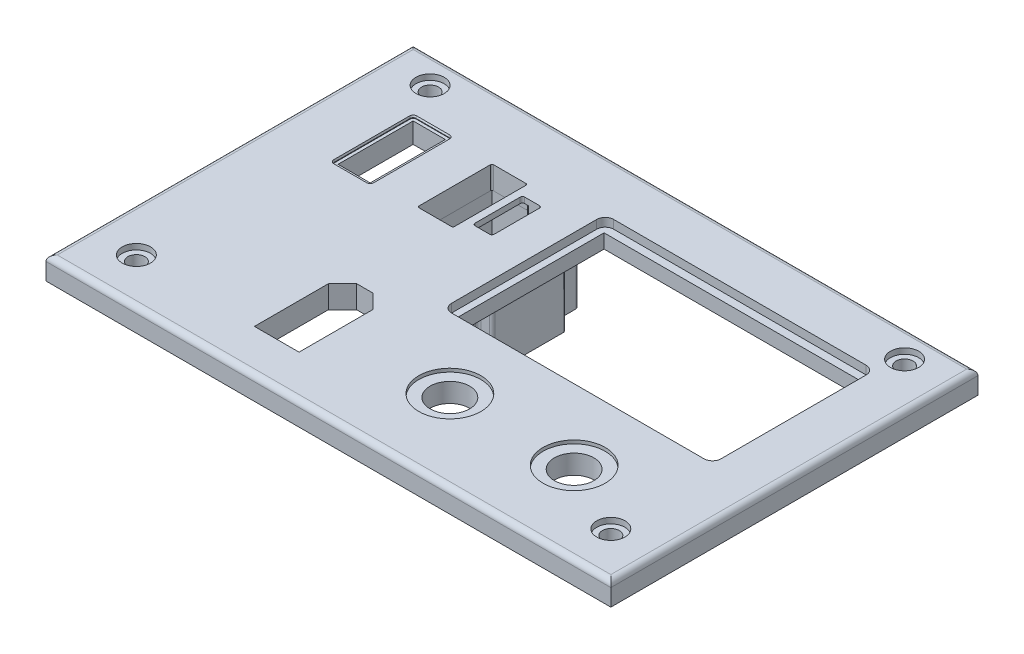
SolidWorks part; units mm, degrees
ref_plane "Спереди" through (0, 0, 0) normal (0, 0, 1) x (1, 0, 0)
ref_plane "Сверху" through (0, 0, 0) normal (0, 1, 0) x (1, 0, 0)
ref_plane "Справа" through (0, 0, 0) normal (1, 0, 0) x (0, 0, -1)
sketch "Эскиз1" plane through (0, 0, 0) normal (0, 1, 0) x (1, 0, 0)
  line L1 (-60, 30) -> (40, 30)
  line L2 (-60, 30) -> (-60, -35)
  line L3 (-60, -35) -> (40, -35)
  line L4 (40, 30) -> (40, -35)
  line L5 (-60, 30) -> (40, -35) construction
  line L6 (-60, -35) -> (40, 30) construction
  point P0 (0, 0)
  dimension "D1" = 65
  dimension "D2" = 100
extrude "Передняя панель основа" add sketch "Эскиз1" along normal blind 4
sketch "Эскиз2" plane through (0, 4, 0) normal (0, 1, 0) x (1, 0, 0)
  line L1 (31, 20.7) -> (-16.7, 20.7)
  line L2 (31, 20.7) -> (31, -8)
  line L3 (31, -8) -> (-16.7, -8)
  line L4 (-16.7, 20.7) -> (-16.7, -8)
  line L5 (31, 20.7) -> (-16.7, -8) construction
  line L6 (31, -8) -> (-16.7, 20.7) construction
  point P0 (7.15, 6.35)
  dimension "D1" = 28.7
  dimension "D2" = 47.7
  dimension "D3" = 27
  dimension "D4" = 9
extrude "Внешняя рамка модуля" cut sketch "Эскиз2" against normal blind 1.5
fillet "Уголки скругления рамки выреза модуля" radius 1.5 4 edges at (31, 3.25, 8) (-16.7, 3.25, 8) (31, 3.25, -20.7) (-16.7, 3.25, -20.7)
sketch "Эскиз3" plane through (0, 2.5, 0) normal (0, 1, 0) x (1, 0, 0)
  line L0 (-60, -35) -> (40, -35) construction
  line L1 (-15.5, 19.3) -> (29.8, 19.3)
  line L2 (-15.5, 19.3) -> (-15.5, -6.6)
  line L3 (-15.5, -6.6) -> (29.8, -6.6)
  line L4 (29.8, 19.3) -> (29.8, -6.6)
  line L5 (-15.5, 19.3) -> (29.8, -6.6) construction
  line L6 (-15.5, -6.6) -> (29.8, 19.3) construction
  line L7 (29.5, 20.7) -> (-15.2, 20.7) construction
  line L8 (-15.2, -8) -> (29.5, -8) construction
  line L9 (31, -6.5) -> (31, 19.2) construction
  line L10 (-16.7, 19.2) -> (-16.7, -6.5) construction
  point P0 (7.15, 6.35)
  dimension "D1" = 25.9
  dimension "D2" = 45.3
  dimension "D3" = 28.4
  dimension "D4" = 10.2
  dimension "D5" = 1.4
  dimension "D6" = 1.4
  dimension "D7" = 1.2
  dimension "D8" = 1.2
extrude "Вырез тела модуля" cut sketch "Эскиз3" against normal blind 3
sketch "Эскиз5" plane through (0, 4, 0) normal (0, 1, 0) x (1, 0, 0)
  line L0 (40, -35) -> (40, 30) construction
  line L4 (-60, -35) -> (40, -35) construction
  circle A1 centre (19, -20.5) radius 5.5
  circle A2 centre (-3, -20.5) radius 5.5
  dimension "D1" = 2
  dimension "D2" = 11
  dimension "D3" = 21
  dimension "D4" = 14.5
extrude "Внешние кольца под бананы" cut sketch "Эскиз5" against normal blind 0.6
sketch "Эскиз7" plane through (0, 4, 0) normal (0, 1, 0) x (1, 0, 0)
  line L1 (-49, 19) -> (-42.2, 19)
  line L2 (-49, 19) -> (-49, 4.6)
  line L3 (-49, 4.6) -> (-42.2, 4.6)
  line L4 (-42.2, 19) -> (-42.2, 4.6)
  line L5 (-49, 19) -> (-42.2, 4.6) construction
  line L6 (-49, 4.6) -> (-42.2, 19) construction
  line L10 (-16.7, 19.2) -> (-16.7, -6.5) construction
  line L11 (29.5, 20.7) -> (-15.2, 20.7) construction
  line L12 (40, 30) -> (-60, 30) construction
  line L13 (-60, 30) -> (-60, -35) construction
  point P0 (-45.6, 11.8)
  dimension "D1" = 14.4
  dimension "D2" = 6.8
  dimension "D3" = 11
  dimension "D4" = 11
extrude "Внешняя рамка USB" cut sketch "Эскиз7" against normal blind 0.4
sketch "Эскиз8" plane through (0, 3.6, 0) normal (0, 1, 0) x (1, 0, 0)
  line L0 (-42.2, 19) -> (-49, 19) construction
  line L1 (-48.45, 18.45) -> (-42.75, 18.45)
  line L2 (-48.45, 18.45) -> (-48.45, 5.15)
  line L3 (-48.45, 5.15) -> (-42.75, 5.15)
  line L4 (-42.75, 18.45) -> (-42.75, 5.15)
  line L5 (-48.45, 18.45) -> (-42.75, 5.15) construction
  line L6 (-48.45, 5.15) -> (-42.75, 18.45) construction
  line L7 (-49, 4.6) -> (-42.2, 4.6) construction
  line L8 (-49, 19) -> (-49, 4.6) construction
  line L9 (-42.2, 4.6) -> (-42.2, 19) construction
  point P0 (-45.6, 11.8)
  dimension "D1" = 13.3
  dimension "D2" = 5.7
  dimension "D3" = 0.55
  dimension "D4" = 0.55
  dimension "D5" = 0.55
  dimension "D6" = 0.55
extrude "USB" cut sketch "Эскиз8" against normal through all
fillet "Скругление уголков 1 USB" radius 0.5 4 edges at (-49, 3.8, -4.6) (-42.2, 3.8, -4.6) (-42.2, 3.8, -19) (-49, 3.8, -19)
sketch "Эскиз9" plane through (0, 4, 0) normal (0, 1, 0) x (1, 0, 0)
  line L0 (-30.6, -27.5) -> (-22.7, -27.5)
  line L1 (-22.7, -27.5) -> (-22.7, -14.4)
  line L2 (-22.7, -14.4) -> (-25.2, -11.9)
  line L3 (-25.2, -11.9) -> (-28.1, -11.9)
  line L4 (-28.1, -11.9) -> (-30.6, -14.4)
  line L5 (-30.6, -14.4) -> (-30.6, -27.5)
  line L6 (-49, 18.5) -> (-49, 5.1) construction
  line L7 (-60, -35) -> (40, -35) construction
  line L8 (-16.7, 19.2) -> (-16.7, -6.5) construction
  point P8 (-26.65, -27.5)
  point P9 (-26.65, -11.9)
  dimension "D4" = 7.5
  dimension "D1" = 7.9
  dimension "D2" = 15.6
  dimension "D3" = 2.5
  dimension "D5" = 6
extrude "XT60 на передней панели" cut sketch "Эскиз9" against normal through all
sketch "Эскиз10" plane through (0, 4, 0) normal (0, 1, 0) x (1, 0, 0)
  line L0 (40, 30) -> (-60, 30) construction
  line L1 (-60, 30) -> (-60, -35) construction
  line L2 (40, -35) -> (40, 30) construction
  line L3 (-60, -35) -> (40, -35) construction
  circle A0 centre (-52, 25) radius 1.5
  circle A1 centre (32, 25) radius 1.5
  circle A2 centre (32, -27) radius 1.5
  circle A3 centre (-52, -27) radius 1.5
  dimension "D1" = 3
  dimension "D2" = 5
  dimension "D3" = 8
  dimension "D5" = 8
  dimension "D6" = 5
  dimension "D7" = 8
  dimension "D8" = 8
  dimension "D9" = 8
  dimension "D10" = 8
  dimension "D4" = 2
extrude "Отверстия крепления передней панели к корпусу" cut sketch "Эскиз10" against normal through all
sketch "Эскиз13" plane through (0, 4, 0) normal (0, 1, 0) x (1, 0, 0)
  circle A0 centre (-52, 25) radius 2.5
  circle A1 centre (32, 25) radius 2.5
  circle A2 centre (32, -27) radius 2.5
  circle A3 centre (-52, -27) radius 2.5
  dimension "D1" = 5
  dimension "D2" = 2
extrude "Фаска под головку болта передней панели" cut sketch "Эскиз13" against normal blind 1
fillet "Скругление1" radius 1 4 edges at (-10, 4, 35) (40, 4, 2.5) (-60, 4, 2.5) (-10, 4, -30)
sketch "Эскиз14" plane through (0, 4, 0) normal (0, 1, 0) x (1, 0, 0)
  line L0 (-28.2, 5.25) -> (-34.5, 5.25)
  line L1 (-34.5, 5.25) -> (-34.5, 18.45)
  line L2 (-34.5, 18.45) -> (-28.2, 18.45)
  line L3 (-28.2, 18.45) -> (-28.2, 21)
  line L4 (-28.2, 21) -> (-26.9, 21)
  line L5 (-26.9, 21) -> (-26.9, 16.25)
  line L6 (-26.9, 16.25) -> (-23.5, 16.25)
  line L7 (-23.5, 16.25) -> (-23.5, 7.45)
  line L8 (-23.5, 7.45) -> (-26.9, 7.45)
  line L9 (-26.9, 7.45) -> (-26.9, 2.7)
  line L10 (-26.9, 2.7) -> (-28.2, 2.7)
  line L11 (-28.2, 2.7) -> (-28.2, 5.25)
  line L12 (-42.75, 18.45) -> (-48.45, 18.45) construction
  dimension "D1" = 13.2
  dimension "D2" = 11
  dimension "D3" = 6.3
  dimension "D4" = 1.3
  dimension "D5" = 3.4
  dimension "D6" = 8.8
  dimension "D7" = 18.3
extrude "Вырез-Вытянуть1" cut sketch "Эскиз14" against normal through all
fillet "Скругление2" radius 0.4 2 edges at (-23.5, 2, -7.45) (-23.5, 2, -16.25)
fillet "Скругление3" radius 0.3 2 edges at (-34.5, 2, -5.25) (-34.5, 2, -18.45)
sketch "Эскиз15" plane through (0, 4, 0) normal (0, 1, 0) x (1, 0, 0)
  line L1 (-28.2, 21.1) -> (-26.9, 21.1)
  line L2 (-28.2, 21.1) -> (-28.2, 2.7)
  line L3 (-28.2, 2.7) -> (-26.9, 2.7)
  line L4 (-26.9, 21.1) -> (-26.9, 2.7)
  line L5 (-28.2, 21.1) -> (-26.9, 2.7) construction
  line L6 (-28.2, 2.7) -> (-26.9, 21.1) construction
  line L11 (-26.9, 21) -> (-28.2, 21) construction
  line L12 (-28.2, 2.7) -> (-26.9, 2.7) construction
  line L15 (-28.2, 21) -> (-28.2, 18.45) construction
  point P0 (-27.55, 11.9)
  point P10 (-27.55, 2.7)
  dimension "D1" = 18.4
extrude "Бобышка-Вытянуть1" add sketch "Эскиз15" against normal blind 1
fillet "Скругление4" radius 0.3 2 edges at (-28.2, 3.5, -5.25) (-28.2, 3.5, -18.45)
fillet "Скругление5" radius 0.4 2 edges at (-26.9, 3.5, -7.45) (-26.9, 3.5, -16.25)
sketch "Эскиз17" plane through (0, 0, 0) normal (0, -1, 0) x (1, 0, 0)
  line L0 (-34.6184, -5.1438) -> (-28.3093, -5.1438)
  line L1 (-28.3093, -5.1438) -> (-28.3093, -2.7009)
  line L2 (-28.3093, -2.7009) -> (-25.8093, -2.7009)
  line L3 (-25.8093, -2.7009) -> (-25.8093, -7.3173)
  line L4 (-25.8093, -7.3173) -> (-23.3093, -7.3173)
  line L5 (-23.3093, -7.3173) -> (-23.3093, -16.3932)
  line L6 (-23.3093, -16.3932) -> (-25.8093, -16.3932)
  line L7 (-25.8093, -16.3932) -> (-25.8093, -21.1023)
  line L8 (-25.8093, -21.1023) -> (-28.3093, -21.1023)
  line L9 (-28.3093, -21.1023) -> (-28.3093, -18.5562)
  line L10 (-28.3093, -18.5562) -> (-34.6184, -18.5562)
  line L11 (-34.6184, -18.5562) -> (-34.6184, -5.1438)
  line L12 (-34.5, -18.15) -> (-34.5, -5.55) construction
  point P14 (-34.5, -11.85)
  point P15 (-34.6184, -11.85)
  dimension "D1" = 2.5
  dimension "D2" = 6.309
  dimension "D3" = 13.4124
  dimension "D4" = 2.5
  dimension "D5" = 9.0759
  dimension "D6" = 18.4013
  dimension "D7" = 2.5461
  dimension "D8" = 4.7091
extrude "Вытянуть-Тонкостенный1" add sketch "Эскиз17" along normal blind 15 thin thin type one direction wall 2
fillet "Скругление6" radius 0.5 12 edges at (-23.8093, -7.5, -18.3932) (-23.8093, -7.5, -23.1023) (-30.3093, -7.5, -23.1023) (-30.3093, -7.5, -20.5562) (-36.6184, -7.5, -20.5562) (-36.6184, -7.5, -3.1438) (-30.3093, -7.5, -3.1438) (-30.3093, -7.5, -0.7009) (-21.3093, -7.5, -18.3932) (-23.8093, -7.5, -5.3173) (-21.3093, -7.5, -5.3173) (-23.8093, -7.5, -0.7009)
sketch "Эскиз18" plane through (0, 0, 0) normal (0, -1, 0) x (1, 0, 0)
  line L1 (-25.8093, -2.7009) -> (-26.9, -2.7009)
  line L2 (-25.8093, -2.7009) -> (-25.8093, -21)
  line L3 (-25.8093, -21) -> (-26.9, -21)
  line L4 (-26.9, -2.7009) -> (-26.9, -21)
extrude "Вырез-Вытянуть2" cut sketch "Эскиз18" against normal blind 3
chamfer "Фаска2" distance 0.3 angle 25 5 edges at (-24.8547, 0, -7.45) (-24.8547, 0, -16.25) (-23.6172, 0, -7.5672) (-23.6172, 0, -16.1328) (-23.5, 0, -11.85) first distance on face at (-25.4031, 2.3333, -7.45) first distance on face at (-25.4031, 2.3333, -16.25) first distance on face at (-23.6586, 2, -7.6086) first distance on face at (-23.6586, 2, -16.0914) first distance on face at (-23.5, 2, -11.85)
chamfer "Фаска3" distance 0.3 angle 25 2 edges at (-27.0047, 0, -21) (-28.2, 0, -19.725) first distance on face at (-27.0047, 1.5, -21) first distance on face at (-28.2, 1.5, -19.725)
chamfer "Фаска4" distance 0.3 angle 25 8 edges at (-42.3464, 4, -4.7464) (-45.6, 4, -4.6) (-42.2, 4, -11.8) (-48.8536, 4, -4.7464) (-42.3464, 4, -18.8536) (-49, 4, -11.8) (-45.6, 4, -19) (-48.8536, 4, -18.8536) first distance on face at (-42.3982, 3.8, -4.7982) first distance on face at (-45.6, 3.8, -4.6) first distance on face at (-42.2, 3.8, -11.8) first distance on face at (-48.8018, 3.8, -4.7982) first distance on face at (-42.3982, 3.8, -18.8018) first distance on face at (-49, 3.8, -11.8) first distance on face at (-45.6, 3.8, -19) first distance on face at (-48.8018, 3.8, -18.8018)
sketch "Эскиз21" plane through (0, 3.4, 0) normal (0, 1, 0) x (1, 0, 0)
  circle A0 centre (-3, -20.5) radius 3.5
  circle A1 centre (19, -20.5) radius 3.5
  dimension "D1" = 7
  dimension "D2" = 2
extrude "Вырез-Вытянуть3" cut sketch "Эскиз21" against normal blind 10
